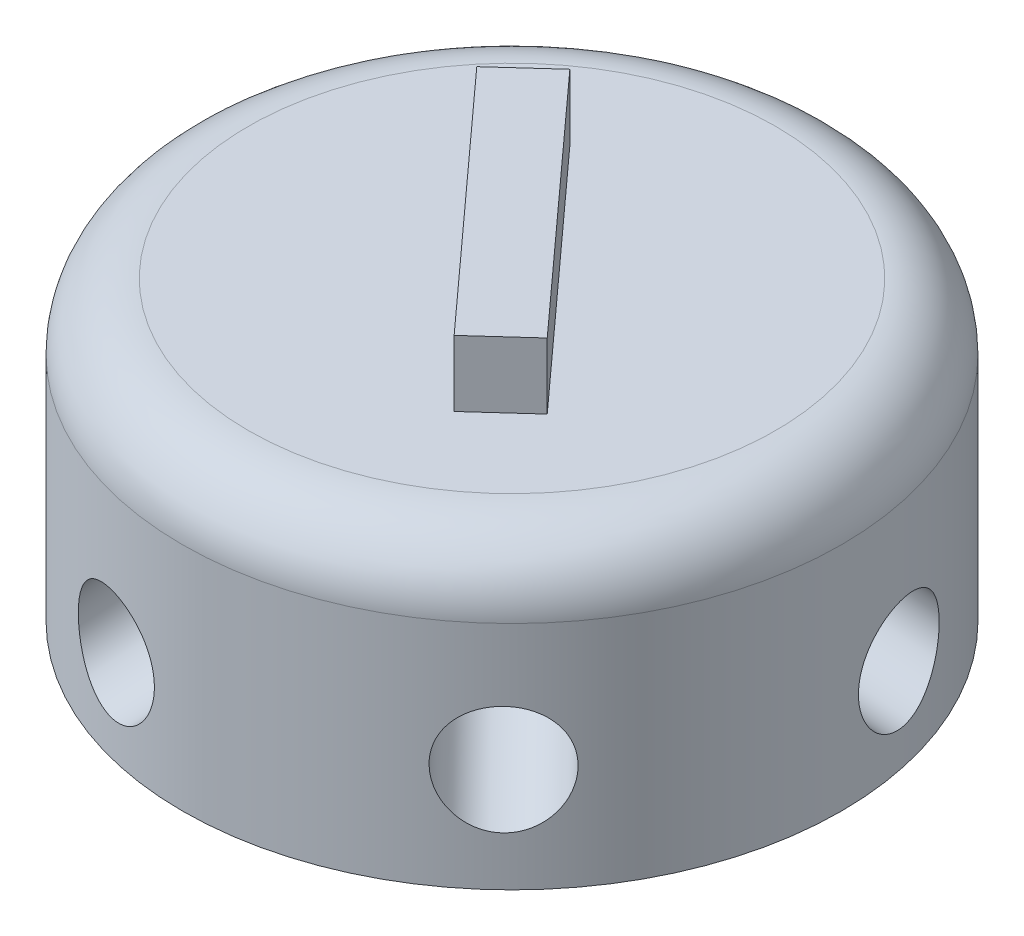
SolidWorks part; units mm, degrees
ref_plane "Front Plane" through (0, 0, 0) normal (0, 0, 1) x (1, 0, 0)
ref_plane "Top Plane" through (0, 0, 0) normal (0, 1, 0) x (1, 0, 0)
ref_plane "Right Plane" through (0, 0, 0) normal (1, 0, 0) x (0, 0, -1)
sketch "Sketch1" plane through (0, 0, 0) normal (0, 1, 0) x (1, 0, 0)
  circle A0 centre (0, 0) radius 10
  dimension "D1" = 20
extrude "base" add sketch "Sketch1" along normal blind 3 and the other way blind 6
ref_axis "6hubaxis" through (0, 5.5, 0) along (0, -1, 0)
ref_plane "Plane1" through (2.6705, -1.0931, 2.7701) normal (-0.6676, 0.2733, -0.6925) x (-0.6559, 0.2243, 0.7208)
sketch "Sketch2" plane through (2.6705, -1.0931, 2.7701) normal (-0.6676, 0.2733, -0.6925) x (-0.6559, 0.2243, 0.7208)
  circle A0 centre (0, 0) radius 1.5 construction
  circle A1 centre (0, 0) radius 1.5 construction
  circle A2 centre (0, 0) radius 1.6
  dimension "D1" = 3.2
extrude "hole1" cut sketch "Sketch2" against normal through all
pattern_circular "hole1mirror" count 2 over 360 about axis through (0, 5.5, 0) along (0, -1, 0) of "hole1"
ref_plane "Plane2" through (-0.9417, -1.2361, 3.6858) normal (0.2354, 0.309, -0.9215) x (-0.9719, 0.0738, -0.2235)
sketch "Sketch3" plane through (-0.9417, -1.2361, 3.6858) normal (0.2354, 0.309, -0.9215) x (-0.9719, 0.0738, -0.2235)
  circle A0 centre (0, 0) radius 1.5 construction
  circle A1 centre (0, 0) radius 1.5 construction
  circle A2 centre (0, 0) radius 1.6
  dimension "D1" = 3.2
extrude "hole2" cut sketch "Sketch3" against normal through all
pattern_circular "hole2mirror" count 2 over 360 about axis through (0, 5.5, 0) along (0, -1, 0) of "hole2"
ref_plane "Plane3" through (-3.7178, -1.2361, 0.8061) normal (0.9295, 0.309, -0.2015) x (-0.1912, -0.0636, -0.9795)
sketch "Sketch4" plane through (-3.7178, -1.2361, 0.8061) normal (0.9295, 0.309, -0.2015) x (-0.1912, -0.0636, -0.9795)
  circle A0 centre (0, 0) radius 1.5 construction
  circle A1 centre (0, 0) radius 1.5 construction
  circle A2 centre (0, 0) radius 1.6
  dimension "D1" = 3.2
extrude "hole3" cut sketch "Sketch4" against normal through all
pattern_circular "hole3mirror" count 2 over 360 about axis through (0, 5.5, 0) along (0, -1, 0) of "hole3"
fillet "Fillet1" radius 2 1 edges at (0, 3, 10)
sketch "Sketch6" plane through (0, 3, 0) normal (0, 1, 0) x (1, 0, 0)
  line L0 (5.3752, -5.9251) -> (-5.3752, 5.9251) construction
  line L1 (-4.1001, 3.0313) -> (-2.6189, 4.3751)
  line L2 (-2.6189, 4.3751) -> (4.1001, -3.0313)
  line L3 (4.1001, -3.0313) -> (2.6189, -4.3751)
  line L4 (2.6189, -4.3751) -> (-4.1001, 3.0313)
  line L5 (-0.7406, -0.6719) -> (0.7406, 0.6719) construction
  circle A0 centre (0, 0) radius 8 construction
  point P6 (0.7406, 0.6719)
  point P9 (-2.4616, 5.2214)
  point P10 (3.3595, -3.7032)
  point P11 (0, 0)
  dimension "D1" = 2
  dimension "D2" = 10
extrude "Boss-Extrude1" add sketch "Sketch6" along normal blind 2
